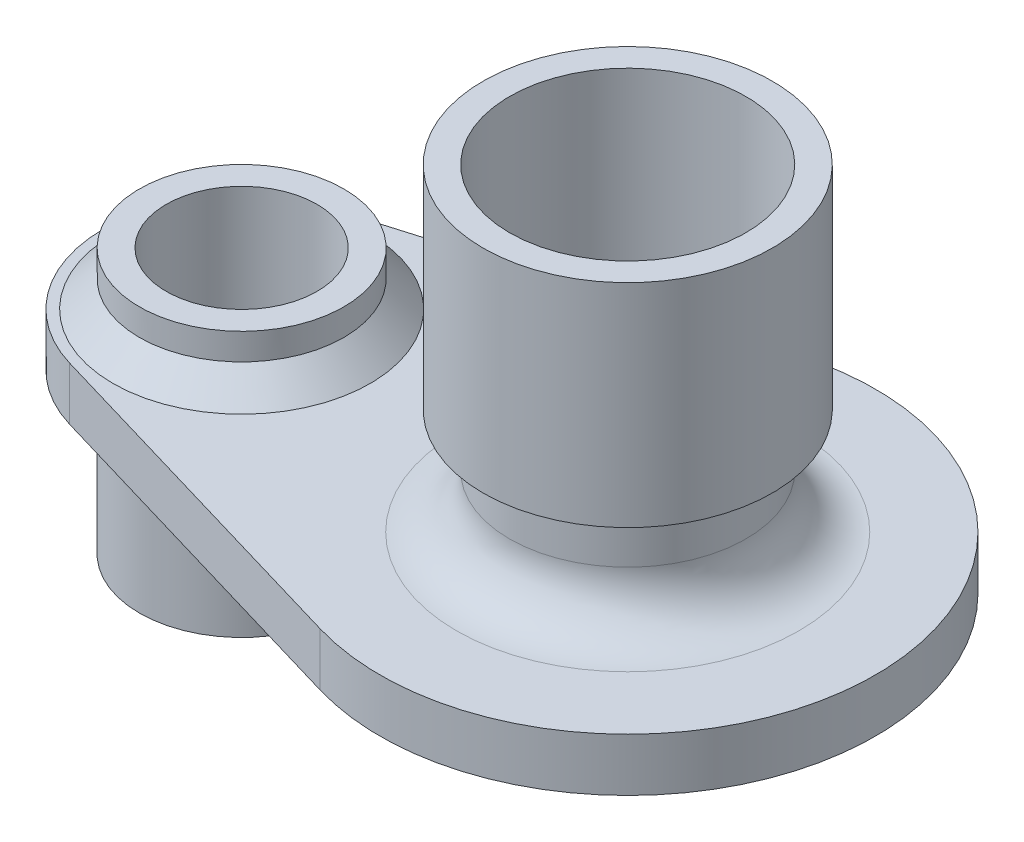
SolidWorks part; units mm, degrees
ref_plane "Front Plane" through (0, 0, 0) normal (0, 0, 1) x (1, 0, 0)
ref_plane "Top Plane" through (0, 0, 0) normal (0, 1, 0) x (1, 0, 0)
ref_plane "Right Plane" through (0, 0, 0) normal (1, 0, 0) x (0, 0, -1)
sketch "Sketch1" plane through (0, 0, 0) normal (0, 1, 0) x (1, 0, 0)
  line L0 (-37.518, 127.1691) -> (302.694, 227.5401)
  line L1 (-37.518, -127.1691) -> (302.694, -227.5401)
  line L2 (0, 0) -> (369.824, 0) construction
  arc A0 (-37.518, 127.1691) -> (-37.518, -127.1691) centre (0, 0) ccw
  arc A1 (302.694, -227.5401) -> (302.694, 227.5401) centre (369.824, 0) ccw
  dimension "D1" = 265.176
  dimension "D2" = 474.472
  dimension "D3" = 369.824
extrude "Boss-Extrude1" add sketch "Sketch1" along normal mid plane 50.8
sketch "Sketch2" plane through (0, -25.4, 0) normal (0, -1, 0) x (1, 0, 0)
  circle A0 centre (0, 0) radius 97.917
  dimension "D1" = 195.834
extrude "Boss-Extrude2" add sketch "Sketch2" along normal blind 152.4
sketch "Sketch3" plane through (0, -177.8, 0) normal (0, -1, 0) x (1, 0, 0)
  circle A0 centre (0, 0) radius 72.263
  circle A1 centre (0, 0) radius 97.917
  circle A2 centre (0, 0) radius 97.917
  dimension "D2" = 144.526
  dimension "D1" = 0
extrude "Cut-Extrude2" cut sketch "Sketch3" against normal through all contours A0
sketch "Sketch4" plane through (0, -177.8, 0) normal (0, -1, 0) x (1, 0, 0)
  circle A1 centre (0, 0) radius 97.917
  circle A2 centre (0, 0) radius 97.917
  dimension "D1" = 0
extrude "Boss-Extrude3" add sketch "Sketch4" against normal blind 254
extrude "Cut-Extrude3" cut sketch "Sketch3<3>" against normal blind 254 contours A0
sketch "Sketch3<3>" plane through (0, -177.8, 0) normal (0, -1, 0) x (1, 0, 0) same geometry as "Sketch3"
sketch "Sketch5" plane through (0, 25.4, 0) normal (0, 1, 0) x (1, 0, 0)
  circle A0 centre (369.824, 0) radius 138.557
  circle A1 centre (369.824, 0) radius 113.157
  dimension "D1" = 277.114
  dimension "D2" = 226.314
extrude "Boss-Extrude5" add sketch "Sketch5" along normal blind 101.6 contours A1
sketch "Sketch8" plane through (0, 127, 0) normal (0, 1, 0) x (1, 0, 0)
  circle A0 centre (369.824, 0) radius 138.557
  circle A1 centre (369.824, 0) radius 113.157
  circle A2 centre (369.824, 0) radius 113.157
  dimension "D2" = 277.114
  dimension "D1" = 0
extrude "Boss-Extrude6" add sketch "Sketch8" along normal blind 203.2 separate body
sketch "Sketch9" plane through (0, 127, 0) normal (0, 1, 0) x (1, 0, 0)
  circle A0 centre (369.824, 0) radius 38.1
  circle A1 centre (369.824, 0) radius 113.157
  circle A2 centre (369.824, 0) radius 113.157
  dimension "D2" = 76.2
  dimension "D1" = 0
extrude "Cut-Extrude6" cut sketch "Sketch9" against normal through all contours A0
fillet "Fillet1" radius 50.8 1 edges at (369.824, 25.4, 113.157)
chamfer "Chamfer1" distance 25.4 angle 45 1 edges at (0, 25.4, 97.917)
equation "\"D2@Sketch1\"=9.34*2"
